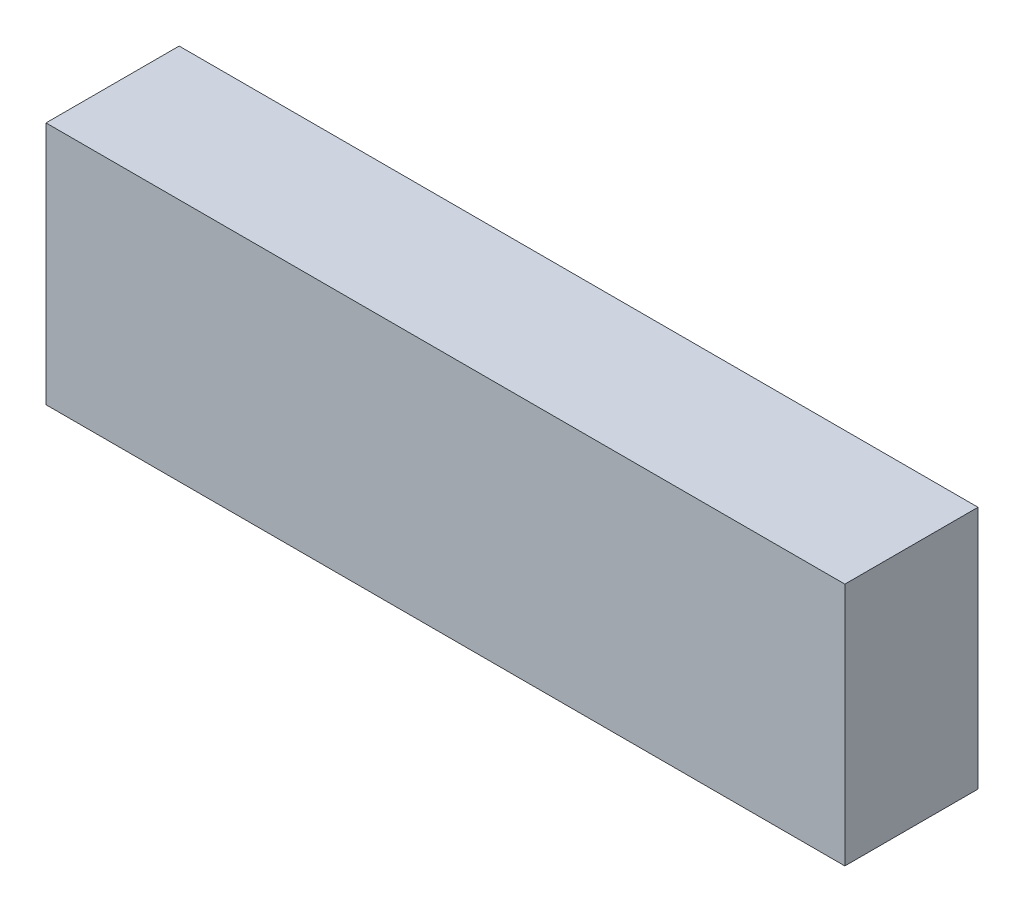
SolidWorks part; units mm, degrees
material "Silicon Dioxide"
ref_plane "Front Plane" through (0, 0, 0) normal (0, 0, 1) x (1, 0, 0)
ref_plane "Top Plane" through (0, 0, 0) normal (0, 1, 0) x (1, 0, 0)
ref_plane "Right Plane" through (0, 0, 0) normal (1, 0, 0) x (0, 0, -1)
sketch "Sketch1" plane through (0, 0, 0) normal (0, 0, 1) x (1, 0, 0)
  line L1 (-75.6362, 48.0134) -> (104.3638, 48.0134)
  line L2 (-75.6362, 48.0134) -> (-75.6362, -6.9866)
  line L3 (-75.6362, -6.9866) -> (104.3638, -6.9866)
  line L4 (104.3638, 48.0134) -> (104.3638, -6.9866)
  dimension "D1" = 180
  dimension "D2" = 55
extrude "Boss-Extrude1" add sketch "Sketch1" along normal blind 30
